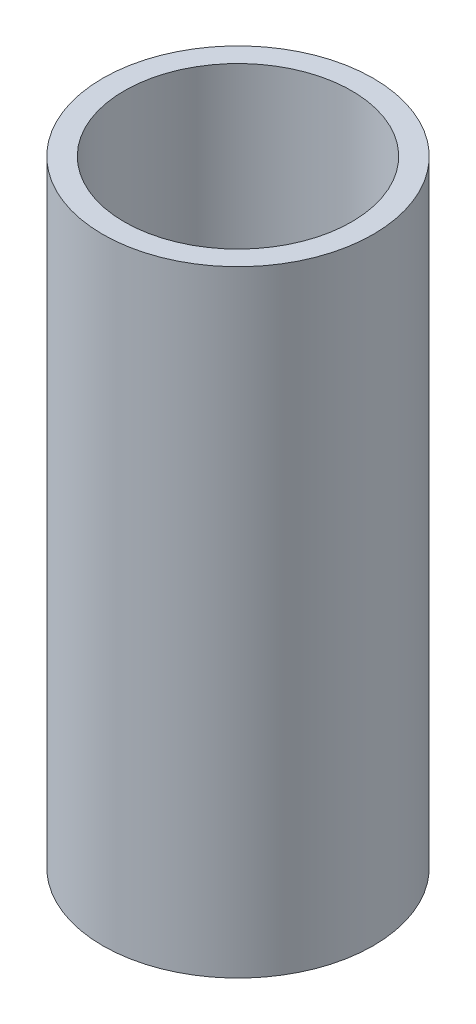
SolidWorks part; units mm, degrees
ref_plane "Front Plane" through (0, 0, 0) normal (0, 0, 1) x (1, 0, 0)
ref_plane "Top Plane" through (0, 0, 0) normal (0, 1, 0) x (1, 0, 0)
ref_plane "Right Plane" through (0, 0, 0) normal (1, 0, 0) x (0, 0, -1)
sketch "Sketch1" plane through (0, 0, 0) normal (0, 1, 0) x (1, 0, 0)
  circle A0 centre (0, 0) radius 32.5
  dimension "SLEEVE_OD" = 65
extrude "Boss-Extrude1" add sketch "Sketch1" along normal blind 148.0458
sketch "Sketch2" plane through (0, 0, 0) normal (0, 1, 0) x (1, 0, 0)
  circle A0 centre (0, 0) radius 27.3121
  dimension "BORE_D" = 54.6241
extrude "Cut-Extrude1" cut sketch "Sketch2" along normal through all
chamfer "Chamfer1" distance 2.8007 angle 45 rebuild error yes
